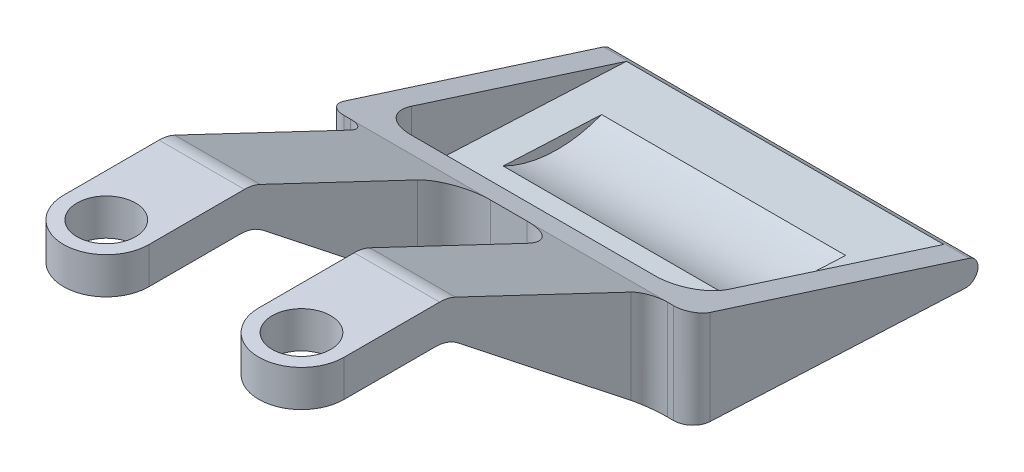
SolidWorks part; units mm, degrees
material "PET"
ref_plane "Front Plane" through (0, 0, 0) normal (0, 0, 1) x (1, 0, 0)
ref_plane "Top Plane" through (0, 0, 0) normal (0, 1, 0) x (1, 0, 0)
ref_plane "Right Plane" through (0, 0, 0) normal (1, 0, 0) x (0, 0, -1)
sketch "Sketch1" plane through (0, 0, 0) normal (1, 0, 0) x (0, 0, -1)
  line L0 (-1000, 0) -> (49000, 0) construction
  line L1 (0, -1000) -> (0, 49000) construction
  line L2 (25, -19.8405) -> (25, -28)
  line L3 (25, -28) -> (55, -29.4148)
  line L4 (55, -29.4148) -> (25, -19.8405)
  line L5 (-966.1685, -28) -> (49033.8315, -28) construction
  dimension "D1" = 2.7
  dimension "D2" = 30
  dimension "D3" = 28
  dimension "D4" = 15
  dimension "D5" = 25
extrude "Boss-Extrude1" add sketch "Sketch1" along normal mid plane 30
ref_plane "Plane1" through (0, -24.7637, 1.1678) normal (0, -0.9989, 0.0471) x (-1, 0, 0)
sketch "Sketch2" plane through (0, 0, 0) normal (0, 1, 0) x (1, 0, 0)
  line L0 (15, 25) -> (-15, 25) construction
  line L1 (-13, 27) -> (13, 27)
  line L2 (-13, 27) -> (-13, 57)
  line L3 (-13, 57) -> (13, 57)
  line L4 (13, 27) -> (13, 57)
  line L5 (-15, 55) -> (-15, 25) construction
  line L6 (0, -1000) -> (0, 49000) construction
  dimension "D1" = 2
  dimension "D2" = 2
  dimension "D3" = 30
extrude "Cut-Extrude1" cut sketch "Sketch2" against normal up to surface (26.0921 mm away) up to plane "Plane1"
sketch "Sketch3" plane through (0, 0, 0) normal (1, 0, 0) x (0, 0, -1)
  line L0 (39, -1000) -> (39, 49000) construction
  line L2 (0, 11.2281) -> (0, -11.2281) construction
  circle A0 centre (39, -17.5) radius 10
  dimension "D2" = 10
  dimension "D1" = 39
  dimension "D3" = 17.5
ref_plane "Plane2" through (0, -13.5, 0) normal (0, 1, 0) x (1, 0, 0)
sketch "Sketch4" plane through (0, -13.5, 0) normal (0, 1, 0) x (1, 0, 0)
  line L0 (0, -1000) -> (0, 49000) construction
  line L1 (-8, -1000) -> (-8, 49000) construction
  line L2 (4.5, -3.5) -> (4.5, 8.5)
  line L3 (-1000, 0) -> (49000, 0) construction
  line L4 (11.5, 8.5) -> (4.5, 8.5)
  line L5 (11.5, -3.5) -> (11.5, 8.5)
  line L6 (-11.5, -3.5) -> (-4.5, -3.5)
  line L7 (-11.5, -3.5) -> (-11.5, 8.5)
  line L8 (-11.5, 8.5) -> (-4.5, 8.5)
  line L9 (-4.5, -3.5) -> (-4.5, 8.5)
  line L10 (11.5, -3.5) -> (4.5, -3.5)
  circle A0 centre (-8, 0) radius 2.4
  circle A1 centre (8, 0) radius 2.4
  dimension "D4" = 4.8
  dimension "D1" = 7
  dimension "D2" = 3.5
  dimension "D3" = 12
  dimension "D5" = 16
extrude "Boss-Extrude2" add sketch "Sketch4" along normal mid plane 3 separate body
sketch "Sketch5" plane through (11.5, 0, 0) normal (1, 0, 0) x (0, 0, -1)
  line L0 (8.5, -12) -> (8.5, -15) construction
  line L1 (25, -19.8405) -> (25, -28) construction
  line L2 (8.5, -12) -> (8.5, -15)
  line L3 (25, -19.8405) -> (25, -28)
  line L4 (8.5, -12) -> (25, -19.8405)
  line L5 (25, -28) -> (8.5, -15)
extrude "Boss-Extrude3" add sketch "Sketch5" against normal up to surface (7 mm away) up to face at (4.5, -13.5, -2.5)
sketch "Sketch8" plane through (-11.5, 0, 0) normal (-1, 0, 0) x (0, 0, 1)
  line L0 (-25, -28) -> (-8.5, -15) construction
  line L1 (-8.5, -12) -> (-25, -19.8405) construction
  line L2 (-25, -19.8405) -> (-25, -28) construction
  line L3 (-8.5, -12) -> (-8.5, -15) construction
  line L4 (-25, -28) -> (-8.5, -15)
  line L5 (-8.5, -12) -> (-25, -19.8405)
  line L6 (-25, -19.8405) -> (-25, -28)
  line L7 (-8.5, -12) -> (-8.5, -15)
extrude "Boss-Extrude4" add sketch "Sketch8" against normal up to surface (7 mm away) up to face at (-4.5, -13.5, -2.5)
fillet "Fillet1" radius 3 8 edges at (8, -15, -8.5) (4.5, -23.9203, -25) (13, -23.2855, -27) (-13, -23.2855, -27) (-8, -15, -8.5) (-4.5, -23.9203, -25) (8, -12, -8.5) (-8, -12, -8.5)
fillet "Fillet2" radius 1.5 4 edges at (-11.5, -23.9203, -25) (-15, -23.9203, -25) (11.5, -23.9203, -25) (15, -23.9203, -25)
fillet "Fillet3" radius 1 1 edges at (0, -29.4148, -55)
fillet "Fillet4" 2 edges at (11.5, -13.5, 3.5) (4.5, -13.5, 3.5) type full round first side face at (11.5, -15.9565, -9.2227) second side face at (4.5, -15.7197, -8.8477) middle face at (8, -13.5, 3.5)
fillet "Fillet5" 2 edges at (-11.5, -13.5, 3.5) (-4.5, -13.5, 3.5) type full round first side face at (-11.5, -15.9565, -9.2227) second side face at (-4.5, -15.7197, -8.8477) middle face at (-8, -13.5, 3.5)
extrude "Cut-Extrude2" cut sketch "Sketch3" against normal mid plane 20
